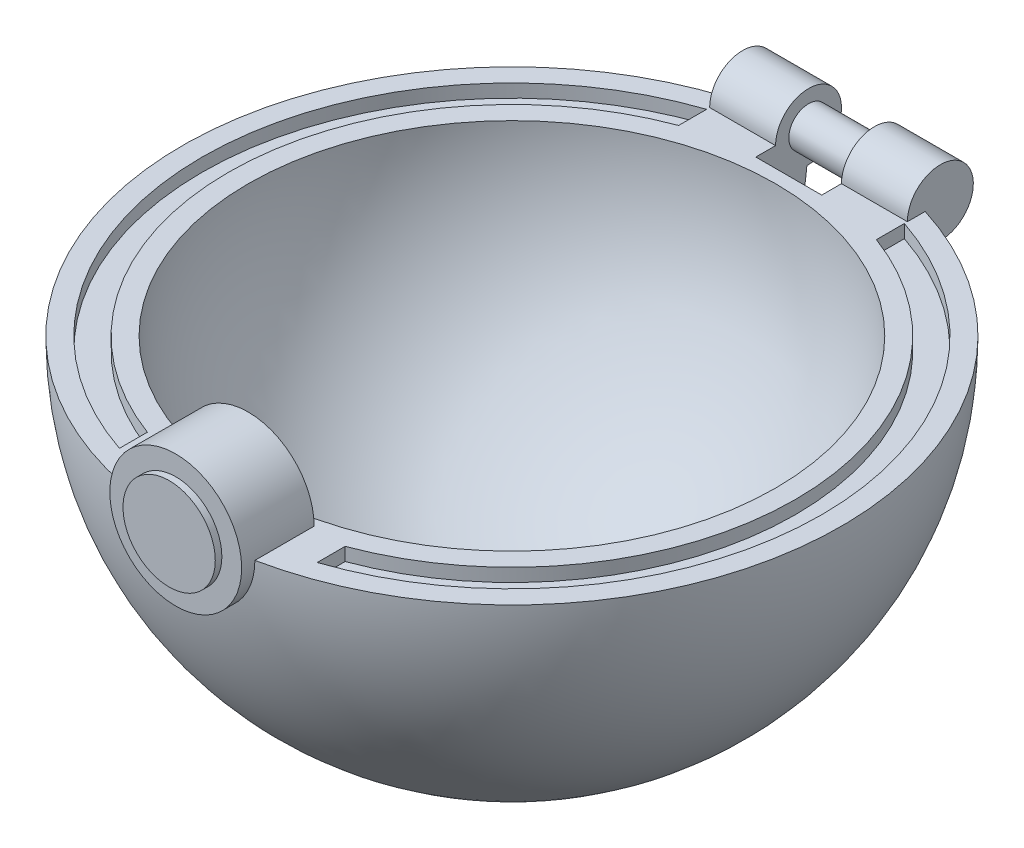
SolidWorks part; units mm, degrees
ref_plane "Front Plane" through (0, 0, 0) normal (0, 0, 1) x (1, 0, 0)
ref_plane "Top Plane" through (0, 0, 0) normal (0, 1, 0) x (1, 0, 0)
ref_plane "Right Plane" through (0, 0, 0) normal (1, 0, 0) x (0, 0, -1)
sketch "Sketch3" plane through (0, 0, 0) normal (1, 0, 0) x (0, 0, -1)
  line L0 (0, 0) -> (0, 30.7446) construction
  line L2 (0, 0) -> (50, 0)
  line L3 (0, 0) -> (0, -50)
  arc A0 (0, -50) -> (50, 0) centre (0, 0) ccw
  arc A1 (0, -40) -> (40, 0) centre (0, 0) ccw
revolve "Revolve2" add sketch "Sketch3" angle 360 about L0 region at (0, -28.7658, -28.7658)
sketch "Sketch5" plane through (0, 0, 0) normal (1, 0, 0) x (0, 0, -1)
  circle A0 centre (50, 0) radius 8
  arc A1 (-50, 0) -> (50, 0) centre (0, 0) ccw construction
extrude "Cut-Extrude1" cut sketch "Sketch5" against normal blind 15 and the other way blind 15 contours A0
sketch "Sketch6" plane through (0, 0, 0) normal (1, 0, 0) x (0, 0, -1)
  circle A0 centre (50, 0) radius 5
extrude "Boss-Extrude1" add sketch "Sketch6" along normal blind 15 and the other way blind 15
sketch "Sketch7" plane through (0, 0, 0) normal (1, 0, 0) x (0, 0, -1)
  circle A0 centre (50, 0) radius 5
extrude "Cut-Extrude2" cut sketch "Sketch7" against normal blind 5 and the other way blind 5
sketch "Sketch8" plane through (0, 0, 0) normal (1, 0, 0) x (0, 0, -1)
  circle A0 centre (50, 0) radius 3
extrude "Boss-Extrude2" add sketch "Sketch8" along normal blind 5 and the other way blind 5
sketch "Sketch9" plane through (15, 0, 0) normal (1, 0, 0) x (0, 0, -1)
  line L1 (50, 0) -> (40, 0)
  line L2 (50, 0) -> (50, -5)
  line L3 (50, -5) -> (40, -5)
  line L4 (40, 0) -> (40, -5)
extrude "Boss-Extrude3" add sketch "Sketch9" against normal blind 10
pattern_linear "LPattern1" count 2 spacing 20 along (-1, 0, 0) of "Boss-Extrude3"
ref_plane "Plane1" through (0, 0, 50) normal (0, 0, 1) x (1, 0, 0)
sketch "Sketch10" plane through (0, 0, 50) normal (0, 0, 1) x (1, 0, 0)
  circle A0 centre (0, 0) radius 10
extrude "Boss-Extrude4" add sketch "Sketch10" along normal blind 1 and the other way blind 10
sketch "Sketch11" plane through (0, 0, 50) normal (0, 0, 1) x (1, 0, 0)
  circle A0 centre (0, 0) radius 7
extrude "Boss-Extrude5" add sketch "Sketch11" along normal blind 2
sketch "Sketch12" plane through (0, 0, 0) normal (0, 1, 0) x (1, 0, 0)
  line L0 (0, 0) -> (0, 67.1927) construction
  line L1 (-15, 44.5421) -> (-15, 40.2989)
  line L2 (-15, 99.9947) -> (-15, -100) construction
  line L3 (15, -100) -> (15, 63.0547) construction
  line L4 (15, 44.5421) -> (15, 40.2989)
  line L5 (-15, -40.2989) -> (-15, -44.5421)
  line L6 (15, -40.2989) -> (15, -44.5421)
  arc A0 (-15, 44.5421) -> (-15, -44.5421) centre (0, 0) ccw
  arc A1 (-15, 40.2989) -> (-15, -40.2989) centre (0, 0) ccw
  arc A2 (15, -40.2989) -> (15, 40.2989) centre (0, 0) ccw
  arc A3 (15, -44.5421) -> (15, 44.5421) centre (0, 0) ccw
  point P7 (0, 18.8774)
  dimension "D1" = 15
  dimension "D2" = 15
extrude "Cut-Extrude5" cut sketch "Sketch12" against normal blind 2
sketch "Sketch13" plane through (0, 0, 0) normal (1, 0, 0) x (0, 0, -1)
  line L1 (49.7494, -5) -> (40, -5)
  line L3 (49.3559, -8) -> (40, -8)
  line L4 (40, -5) -> (40, -8)
  arc A0 (49.3559, -8) -> (49.7494, -5) centre (0, 0) ccw
extrude "Boss-Extrude6" add sketch "Sketch13" along normal blind 15 and the other way blind 15
sketch "Sketch14" plane through (0, 0, 0) normal (1, 0, 0) x (0, 0, -1)
  line L1 (49.7494, -5) -> (40, -5)
  line L3 (49.3559, -8) -> (40, -8)
  line L4 (40, -5) -> (40, -8)
  arc A0 (49.3559, -8) -> (49.7494, -5) centre (0, 0) ccw
extrude "Cut-Extrude6" cut sketch "Sketch14" against normal blind 5 and the other way blind 5
ref_plane "Plane2" through (0, -50, 0) normal (0, 1, 0) x (1, 0, 0)
sketch "Sketch15" plane through (0, -50, 0) normal (0, 1, 0) x (1, 0, 0)
  circle A0 centre (0, 0) radius 10
extrude "Cut-Extrude7" cut sketch "Sketch15" along normal blind 1
